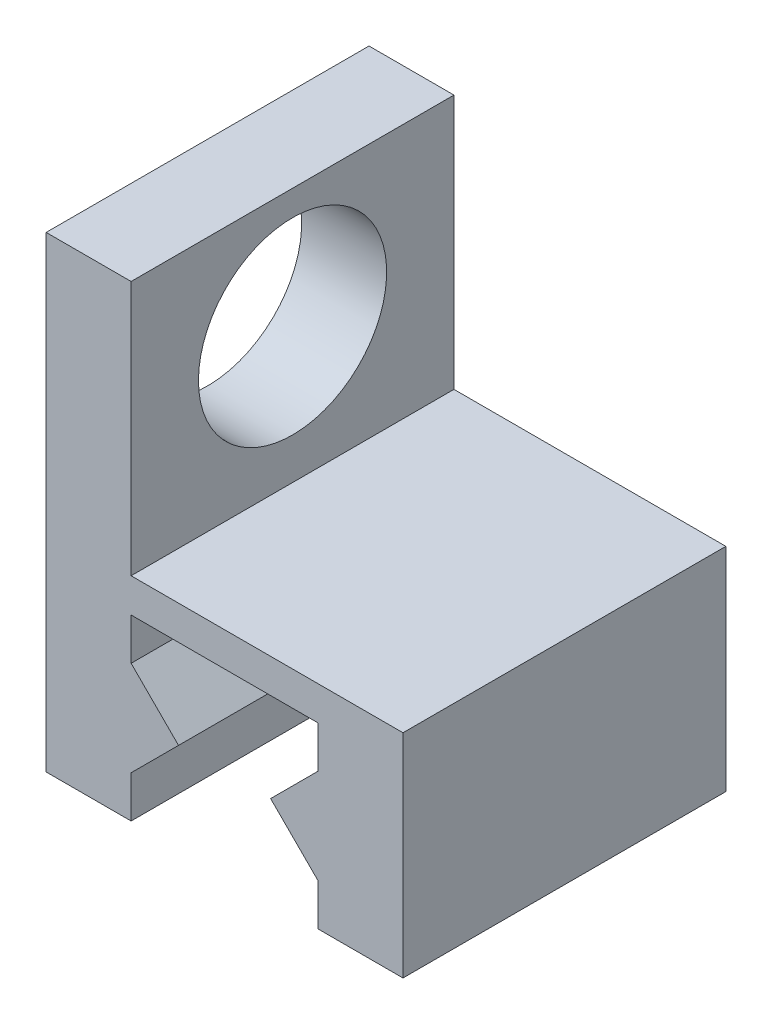
SolidWorks part; units mm, degrees
ref_plane "Front Plane" through (0, 0, 0) normal (0, 0, 1) x (1, 0, 0)
ref_plane "Top Plane" through (0, 0, 0) normal (0, 1, 0) x (1, 0, 0)
ref_plane "Right Plane" through (0, 0, 0) normal (1, 0, 0) x (0, 0, -1)
sketch "Sketch1" plane through (0, 0, 0) normal (0, 0, 1) x (1, 0, 0)
  line L0 (-11, 0) -> (11, 0)
  line L1 (11, 0) -> (11, -4.92)
  line L2 (11, -4.92) -> (5.42, -10.5)
  line L3 (5.42, -10.5) -> (11, -10.5) construction
  line L4 (11, -16.08) -> (5.42, -10.5)
  line L5 (11, -16.08) -> (11, -21)
  line L6 (0, 0) -> (0, -50000) construction
  line L7 (11, -21) -> (21, -21)
  line L8 (21, -21) -> (21, 4)
  line L9 (21, 4) -> (-21, 4)
  line L10 (-5.42, -10.5) -> (-11, -10.5) construction
  line L11 (-21, -21) -> (-21, 4)
  line L12 (-11, -21) -> (-21, -21)
  line L13 (-11, -16.08) -> (-11, -21)
  line L14 (-11, -16.08) -> (-5.42, -10.5)
  line L15 (-11, -4.92) -> (-5.42, -10.5)
  line L16 (-11, 0) -> (-11, -4.92)
  point P16 (0, 4)
  point P21 (0, 0)
  dimension "D1" = 11
  dimension "D2" = 4.92
  dimension "D3" = 7.8913
  dimension "D4" = 45
  dimension "D5" = 4.92
  dimension "D6" = 10
  dimension "D7" = 25
extrude "Boss-Extrude1" add sketch "Sketch1" along normal mid plane 38
sketch "Sketch2" plane through (0, 4, 0) normal (0, 1, 0) x (1, 0, 0)
  line L0 (21, -19) -> (-21, -19) construction
  line L1 (-21, 19) -> (-11, 19)
  line L2 (-21, 19) -> (-21, -19)
  line L3 (-21, -19) -> (-11, -19)
  line L4 (-11, 19) -> (-11, -19)
  dimension "D1" = 10
extrude "Boss-Extrude2" add sketch "Sketch2" along normal blind 30
sketch "Sketch3" plane through (-21, 0, 0) normal (-1, 0, 0) x (0, 0, 1)
  line L0 (0, 0) -> (0, 34) construction
  line L1 (-19, 34) -> (19, 34) construction
  circle A0 centre (0, 19.925) radius 11.075
  point P7 (0, 31)
  dimension "D1" = 22.15
  dimension "D2" = 3
extrude "Cut-Extrude1" cut sketch "Sketch3" against normal up to next
ref_axis "Axis1" through (-11, 19.925, 0) along (-1, 0, 0)
